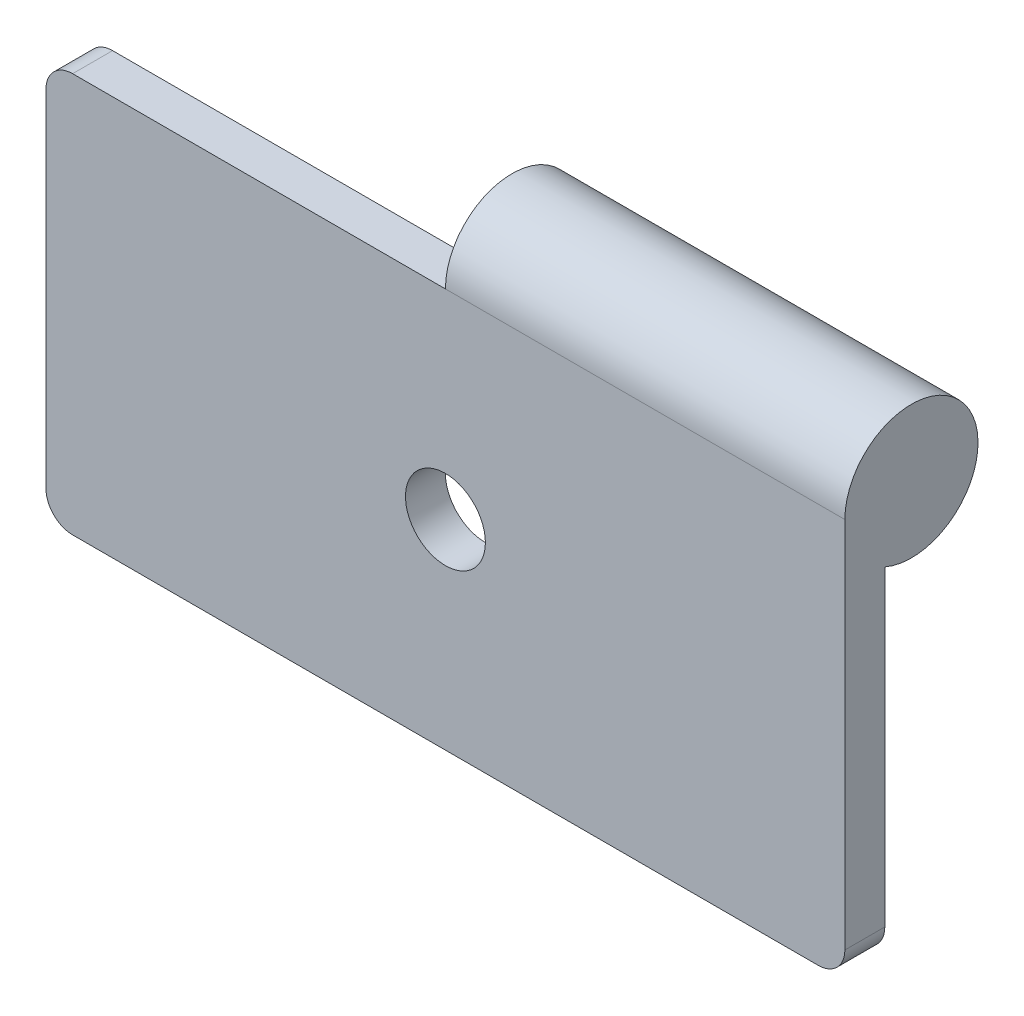
SolidWorks part; units mm, degrees
ref_plane "前视基准面" through (0, 0, 0) normal (0, 0, 1) x (1, 0, 0)
ref_plane "上视基准面" through (0, 0, 0) normal (0, 1, 0) x (1, 0, 0)
ref_plane "右视基准面" through (0, 0, 0) normal (1, 0, 0) x (0, 0, -1)
sketch "草图1" plane through (0, 0, 0) normal (0, 0, 1) x (1, 0, 0)
  line L1 (-15, -7.5) -> (15, -7.5)
  line L2 (-15, -7.5) -> (-15, 7.5)
  line L3 (-15, 7.5) -> (15, 7.5)
  line L4 (15, -7.5) -> (15, 7.5)
  line L5 (-15, -7.5) -> (15, 7.5) construction
  line L6 (-15, 7.5) -> (15, -7.5) construction
  point P1 (0, 0)
  dimension "D1" = 15
  dimension "D2" = 30
base flange "基体-法兰1" sketch "草图1" thickness 1.5 reverse thickness direction no parameters "D1"=10
sketch "草图6" plane through (15, 0, 0) normal (1, 0, 0) x (0, 0, -1)
  circle A1 centre (2.5, 7.5) radius 2.5
  dimension "D1" = 5
extrude "凸台-拉伸1" add sketch "草图6" against normal blind 15
sketch "草图7" plane through (0, 0, 0) normal (0, 0, 1) x (1, 0, 0)
  circle A0 centre (0, 0) radius 1.5
  dimension "D1" = 3
extrude "切除-拉伸1" cut sketch "草图7" against normal blind 15 normal cut yes
fillet "圆角1" radius 1 3 edges at (15, -7.5, -0.75) (-15, -7.5, -0.75) (-15, 7.5, -0.75)
sketch "折弯-线1" [suppressed] plane through (0, 0, 0) normal (0, 1, 0) x (1, 0, 0)
sketch "边界框1" [suppressed] plane through (0, 0, 0) normal (0, 1, 0) x (1, 0, 0)
sheet metal parameters "钣金1" thickness 1.5 parameters "D1"=10
flat pattern "平板型式1" [suppressed]
sketch "折弯-线2" plane through (0, 0, 0) normal (0, 1, 0) x (1, 0, 0)
sketch3d "边界框2" [suppressed]
  line L0 (15, -7.5, 0) -> (-15, -7.5, 0) construction
  line L1 (15, 7.5, 0) -> (-15, 7.5, 0) construction
  line L2 (15, -7.5, 0) -> (15, 7.5, 0) construction
  line L3 (-15, -7.5, 0) -> (-15, 7.5, 0) construction
sheet metal parameters "钣金2" thickness 1.5 parameters "D1"=10
flat pattern "平板型式1"
sketch "折弯-线2" plane through (0, 0, 0) normal (0, 1, 0) x (1, 0, 0)
sketch3d "边界框2" [suppressed]
  line L0 (-15, -7.5, 0) -> (15, -7.5, 0) construction
  line L1 (-15, 7.5, 0) -> (15, 7.5, 0) construction
  line L2 (-15, -7.5, 0) -> (-15, 7.5, 0) construction
  line L3 (15, -7.5, 0) -> (15, 7.5, 0) construction
sheet metal parameters "钣金3" thickness 1.5 parameters "D1"=10
flat pattern "平板型式1"
sketch "折弯-线2" plane through (0, 0, 0) normal (0, 1, 0) x (1, 0, 0)
sketch3d "边界框2" [suppressed]
  line L0 (-15, -7.5, 0) -> (15, -7.5, 0) construction
  line L1 (-15, 7.5, 0) -> (15, 7.5, 0) construction
  line L2 (-15, -7.5, 0) -> (-15, 7.5, 0) construction
  line L3 (15, -7.5, 0) -> (15, 7.5, 0) construction
